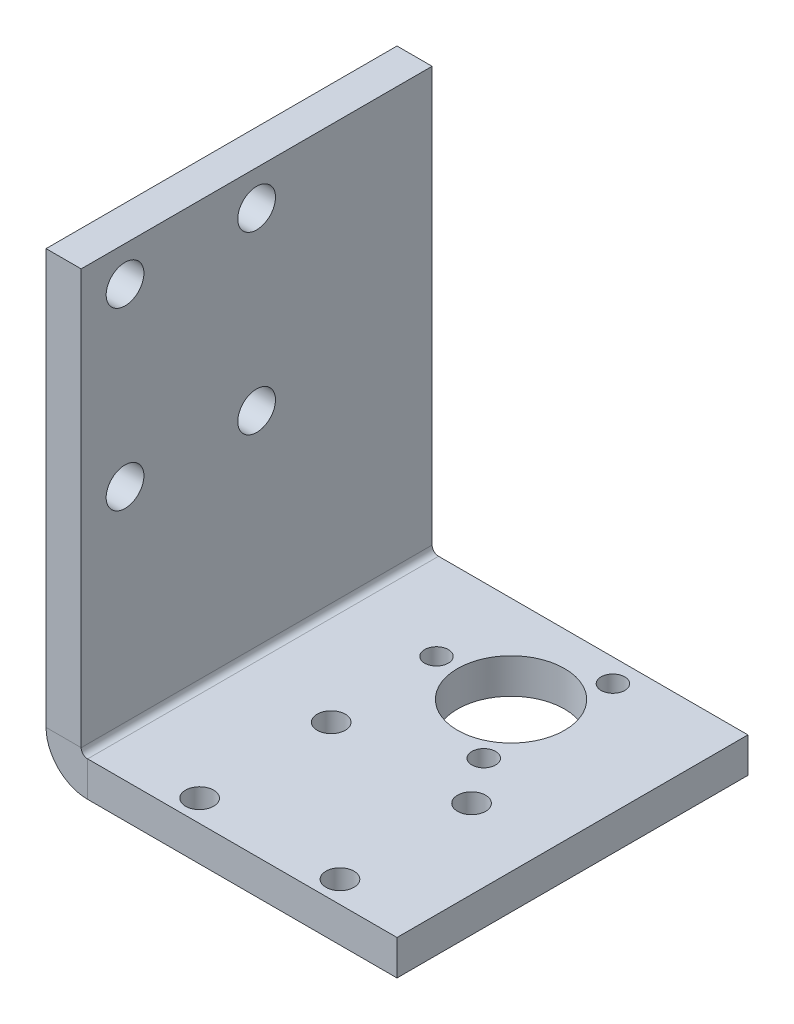
SolidWorks part; units mm, degrees
note: The reader was unsure of these and kept them because the rebuilt part matched: thickness of "基材-凸緣2", "鈑金4", "鈑金5", "鈑金6", "鈑金7", "鈑金8", "鈑金9", "鈑金12"; bend radius of "基材彎折1".
material "AISI 304"
ref_plane "前基準面" through (0, 0, 0) normal (0, 0, 1) x (1, 0, 0)
ref_plane "上基準面" through (0, 0, 0) normal (0, 1, 0) x (1, 0, 0)
ref_plane "右基準面" through (0, 0, 0) normal (1, 0, 0) x (0, 0, -1)
sketch "草圖16" plane through (0, 0, 0) normal (0, 0, 1) x (1, 0, 0)
  line L0 (0, 0) -> (0, 48)
  line L1 (0, 0) -> (36, 0)
  dimension "D1" = 36
  dimension "D2" = 48
base flange "基材-凸緣2" sketch "草圖16" end condition mid plane depth 40 reverse direction no thickness 4 reverse thickness direction no bend radius 0.7366
bend "基材彎折1" bend radius 0.7366 bend angle 90 parameters "D5"=1
sketch "草圖21" plane through (-4, 0, 0) normal (-1, 0, 0) x (0, 0, 1)
  line L0 (20, 0) -> (-20, 0) construction
  line L1 (2, 0.7366) -> (15.5, 0.7366)
  line L2 (2, 0.7366) -> (2, 22)
  line L3 (2, 22) -> (15.5, 22)
  line L4 (15.5, 0.7366) -> (15.5, 22)
  line L5 (2, 0.7366) -> (15.5, 22) construction
  line L6 (2, 22) -> (15.5, 0.7366) construction
  line L7 (-20, 48) -> (-20, 0.7366) construction
  line L9 (20, 0.7366) -> (-20, 0.7366) construction
  point P4 (8.75, 11.3683)
  dimension "D1" = 22
  dimension "D2" = 13.5
  dimension "D3" = 22
extrude "除料-伸長1" [suppressed] cut sketch "草圖21" against normal blind 20
hole_wizard "M3 餘隙孔1" positions "草圖22" profile "草圖23" hole size "M3" standard "Ansi Metric" end condition through all
sketch "草圖22" plane through (0, 0, 0) normal (0, -1, 0) x (-1, 0, 0)
  line L1 (-11, -2.5) -> (-27, -2.5) construction
  line L2 (-11, -2.5) -> (-11, -17.5) construction
  line L3 (-11, -17.5) -> (-27, -17.5) construction
  line L4 (-27, -2.5) -> (-27, -17.5) construction
  line L5 (-11, -2.5) -> (-27, -17.5) construction
  line L6 (-11, -17.5) -> (-27, -2.5) construction
  line L11 (4, -20) -> (4, 20) construction
  line L13 (-0.7366, -20) -> (-36, -20) construction
  point P2 (-27, -17.5)
  point P57 (-11, -2.5)
  point P58 (-11, -17.5)
  point P59 (-27, -2.5)
  point P95 (-19, -10)
  dimension "D1" = 16
  dimension "D2" = 15
  dimension "D3" = 10
  dimension "D4" = 15
sketch "草圖23" plane through (27, 0, 17.5) normal (1, 0, 0) x (0, 0, 1)
  line L0 (0, 0) -> (0, 4)
  line L1 (0, 4) -> (1.6, 4)
  line L2 (1.6, 4) -> (1.6, 0)
  line L5 (1.6, 0) -> (0, 0)
  line L11 (0, -6.35) -> (0, 107.95) construction
  dimension "砮 ふ 畖" = 3.2
  dimension "砮 ふ瞏 " = 4
sketch "草圖24" plane through (0, -4, 0) normal (0, -1, 0) x (1, 0, 0)
  line L0 (19, 10) -> (19, -10) construction
  line L1 (11, 17.5) -> (27, 17.5) construction
  line L2 (11, 17.5) -> (11, 2.5) construction
  line L3 (11, 2.5) -> (27, 2.5) construction
  line L4 (27, 17.5) -> (27, 2.5) construction
  line L5 (11, 17.5) -> (27, 2.5) construction
  line L6 (11, 2.5) -> (27, 17.5) construction
  circle A0 centre (19, -10) radius 6.1
  point P4 (19, 10)
  point P13 (19, -10)
  dimension "D1" = 12.2
  dimension "D2" = 20
extrude "除料-伸長2" cut sketch "草圖24" against normal through all normal cut yes
hole_wizard "M4 餘隙孔1" positions "草圖27" profile "草圖28" hole size "M4" standard "Ansi Metric" end condition through all
sketch "草圖27" plane through (0, 0, 0) normal (-1, 0, 0) x (0, 0, 1)
  line L1 (15, 44) -> (-15, 44) construction
  line L2 (15, 44) -> (15, 24) construction
  line L3 (15, 24) -> (-15, 24) construction
  line L4 (-15, 44) -> (-15, 24) construction
  line L5 (15, 44) -> (-15, 24) construction
  line L6 (15, 24) -> (-15, 44) construction
  line L7 (0, 0) -> (0, 34) construction
  line L10 (20, 48) -> (-20, 48) construction
  point P104 (15, 44)
  point P105 (15, 24)
  point P133 (0, 24)
  point P135 (0, 44)
  dimension "D1" = 30
  dimension "D2" = 20
  dimension "D3" = 14
sketch "草圖28" plane through (0, 44, 0) normal (0, 1, 0) x (0, 0, -1)
  line L0 (0, 0) -> (0, 4)
  line L1 (0, 4) -> (2.15, 4)
  line L2 (2.15, 4) -> (2.15, 0)
  line L5 (2.15, 0) -> (0, 0)
  line L11 (0, -6.35) -> (0, 107.95) construction
  dimension "砮 ふ 畖" = 4.3
  dimension "砮 ふ瞏 " = 4
hole_wizard "M2.5 餘隙孔1" positions "草圖25" profile "草圖26" hole size "M2.5" standard "Ansi Metric" end condition through all
sketch "草圖25" plane through (0, -4, 0) normal (0, -1, 0) x (-1, 0, 0)
  line L1 (-10.5, 10) -> (-19, 10) construction
  circle A1 centre (-19, 10) radius 6.1 construction
  point P0 (-10.5, 10)
  dimension "D1" = 8.5
sketch "草圖26" plane through (10.5, -4, -10) normal (1, 0, 0) x (0, 0, -1)
  line L0 (0, 0) -> (0, 52)
  line L1 (0, 52) -> (1.35, 52)
  line L2 (1.35, 52) -> (1.35, 0)
  line L5 (1.35, 0) -> (0, 0)
  line L11 (0, -6.35) -> (0, 107.95) construction
  dimension "砮 ふ 畖" = 2.7
  dimension "砮 ふ瞏 " = 52
pattern_circular "環狀複製排列1" count 3 over 360 about axis through (19, 0, -10) along (0, 1, 0) of "M2.5 餘隙孔1"
sketch "彎折-線3" [suppressed] plane through (0, 0, 0) normal (0, 1, 0) x (1, 0, 0)
sketch "邊界方塊3" [suppressed] plane through (0, 0, 0) normal (0, 1, 0) x (1, 0, 0)
sheet metal parameters "鈑金4" thickness 4 parameters "D1"=0.7366
flat pattern "平板-型式4" [suppressed]
sketch "彎折-線4" plane through (0, 0, 0) normal (0, 1, 0) x (1, 0, 0)
  line L0 (-1.4127, -20) -> (-1.4127, 20) construction
  line L1 (-1.4127, -20) -> (-1.4127, 20) construction
sketch3d "邊界方塊4" [suppressed]
  line L0 (60, 0, 0) -> (-32.8254, 0, 0) construction
  line L1 (60, 40, 0) -> (-32.8254, 40, 0) construction
  line L2 (60, 0, 0) -> (60, 40, 0) construction
  line L3 (-32.8254, 0, 0) -> (-32.8254, 40, 0) construction
bend of the flat pattern "平板-<基材彎折1>1"
sheet metal parameters "鈑金5" thickness 4 parameters "D1"=0.7366
flat pattern "平板-型式4"
sketch "彎折-線4" plane through (0, 0, 0) normal (0, 1, 0) x (1, 0, 0)
  line L0 (-1.4127, -20) -> (-1.4127, -14) construction
  line L1 (-1.4127, -20) -> (-1.4127, -14) construction
  line L2 (-1.4127, 1) -> (-1.4127, 20) construction
sketch3d "邊界方塊4" [suppressed]
  line L0 (60, 0, 0) -> (-42.8254, 0, 0) construction
  line L1 (60, 40, 0) -> (-42.8254, 40, 0) construction
  line L2 (60, 0, 0) -> (60, 40, 0) construction
  line L3 (-42.8254, 0, 0) -> (-42.8254, 40, 0) construction
bend of the flat pattern "平板-<基材彎折1>1"
sheet metal parameters "鈑金6" thickness 4 parameters "D1"=0.7366
flat pattern "平板-型式4"
sketch "彎折-線4" plane through (0, 0, 0) normal (0, 1, 0) x (1, 0, 0)
  line L0 (-1.4127, -20) -> (-1.4127, 20) construction
  line L1 (-1.4127, -20) -> (-1.4127, 20) construction
sketch3d "邊界方塊4" [suppressed]
  line L0 (40, 0, 0) -> (-42.8254, 0, 0) construction
  line L1 (40, 40, 0) -> (-42.8254, 40, 0) construction
  line L2 (40, 0, 0) -> (40, 40, 0) construction
  line L3 (-42.8254, 0, 0) -> (-42.8254, 40, 0) construction
bend of the flat pattern "平板-<基材彎折1>1"
sheet metal parameters "鈑金7" thickness 4 parameters "D1"=0.7366
flat pattern "平板-型式4"
sketch "彎折-線4" plane through (0, 0, 0) normal (0, 1, 0) x (1, 0, 0)
  line L0 (-1.4127, -20) -> (-1.4127, 20) construction
  line L1 (-1.4127, -20) -> (-1.4127, 20) construction
sketch3d "邊界方塊4" [suppressed]
  line L0 (40, 0, 0) -> (-42.8254, 0, 0) construction
  line L1 (40, 40, 0) -> (-42.8254, 40, 0) construction
  line L2 (40, 0, 0) -> (40, 40, 0) construction
  line L3 (-42.8254, 0, 0) -> (-42.8254, 40, 0) construction
bend of the flat pattern "平板-<基材彎折1>1"
sheet metal parameters "鈑金8" thickness 4 parameters "D1"=0.7366
flat pattern "平板-型式4"
sketch "彎折-線4" plane through (0, 0, 0) normal (0, 1, 0) x (1, 0, 0)
  line L0 (-1.4127, -20) -> (-1.4127, 20) construction
  line L1 (-1.4127, -20) -> (-1.4127, 20) construction
sketch3d "邊界方塊4" [suppressed]
  line L0 (36, 0, 0) -> (-50.8254, 0, 0) construction
  line L1 (36, 40, 0) -> (-50.8254, 40, 0) construction
  line L2 (36, 0, 0) -> (36, 40, 0) construction
  line L3 (-50.8254, 0, 0) -> (-50.8254, 40, 0) construction
bend of the flat pattern "平板-<基材彎折1>1"
sheet metal parameters "鈑金9" thickness 4 parameters "D1"=0.7366
flat pattern "平板-型式4"
sketch "彎折-線4" plane through (0, 0, 0) normal (0, 1, 0) x (1, 0, 0)
  line L0 (-1.02, -30) -> (-1.02, 30) construction
  line L1 (-1.02, -30) -> (-1.02, 30) construction
sketch3d "邊界方塊4" [suppressed]
  line L0 (40, 0, 0) -> (-52.04, 0, 0) construction
  line L1 (40, 60, 0) -> (-52.04, 60, 0) construction
  line L2 (40, 0, 0) -> (40, 60, 0) construction
  line L3 (-52.04, 0, 0) -> (-52.04, 60, 0) construction
bend of the flat pattern "平板-<基材彎折1>1"
sheet metal parameters "鈑金12" thickness 4 parameters "D1"=0.7366
flat pattern "平板-型式4"
sketch "彎折-線4" plane through (0, 0, 0) normal (0, 1, 0) x (1, 0, 0)
  line L0 (-1.4127, -20) -> (-1.4127, 20) construction
  line L1 (-1.4127, -20) -> (-1.4127, 20) construction
sketch3d "邊界方塊4" [suppressed]
  line L0 (36, 0, 0) -> (-50.8254, 0, 0) construction
  line L1 (36, 40, 0) -> (-50.8254, 40, 0) construction
  line L2 (36, 0, 0) -> (36, 40, 0) construction
  line L3 (-50.8254, 0, 0) -> (-50.8254, 40, 0) construction
bend of the flat pattern "平板-<基材彎折1>1"
